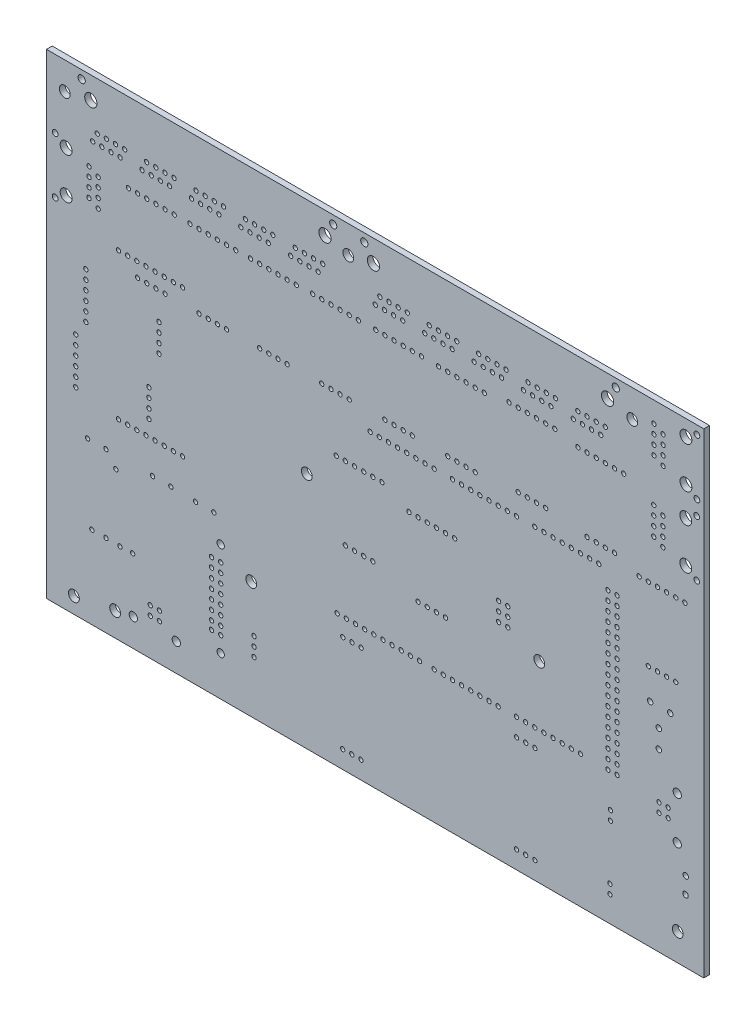
SolidWorks part; units mm, degrees
ref_plane "Front Plane" through (0, 0, 0) normal (0, 0, 1) x (1, 0, 0)
ref_plane "Top Plane" through (0, 0, 0) normal (0, 1, 0) x (1, 0, 0)
ref_plane "Right Plane" through (0, 0, 0) normal (1, 0, 0) x (0, 0, -1)
sketch "Model" plane through (0, 0, 0) normal (0, 0, 1) x (1, 0, 0)
  line L0 (-2.54, -132.08) -> (180, -132.08)
  line L1 (180, -132.08) -> (180, 0)
  line L2 (-2.54, 0) -> (180, 0)
  line L3 (-2.54, -132.08) -> (-2.54, 0)
  line L4 (55.118, -104.267) -> (55.118, -122.428) construction
  line L5 (70.8377, -127.159) -> (150.1297, -127.159) construction
  line L6 (71.3748, -100.203) -> (143.2189, -100.203) construction
  line L7 (154.083, -100.203) -> (154.083, -127.0359) construction
  line L8 (156.083, -101.2392) -> (155.956, -126.5721) construction
  line L9 (158.9458, -104.6525) -> (151.384, -104.6525) construction
  circle A0 centre (175, -109.9998) radius 0.762
  circle A2 centre (21.3998, -109.2497) radius 0.6
  circle A4 centre (10.0742, -109.2244) radius 0.6
  circle A6 centre (13.9749, -109.2495) radius 0.6
  circle A8 centre (165.1, -73.025) radius 0.762
  circle A76 centre (43.307, -99.187) radius 0.6
  circle A78 centre (43.307, -101.727) radius 0.6
  circle A80 centre (43.307, -104.267) radius 0.6
  circle A82 centre (43.307, -106.807) radius 0.6
  circle A84 centre (43.307, -109.347) radius 0.6
  circle A86 centre (43.307, -111.887) radius 0.6
  circle A88 centre (43.307, -114.427) radius 0.6
  circle A90 centre (43.307, -116.713) radius 0.6
  circle A92 centre (45.847, -99.187) radius 0.6
  circle A94 centre (45.847, -101.727) radius 0.6
  circle A96 centre (45.847, -104.267) radius 0.6
  circle A98 centre (45.847, -106.807) radius 0.6
  circle A100 centre (45.847, -109.347) radius 0.6
  circle A102 centre (45.847, -111.887) radius 0.6
  circle A104 centre (45.847, -114.427) radius 0.6
  circle A106 centre (45.847, -116.713) radius 0.6
  circle A108 centre (20, -78.994) radius 0.6
  circle A110 centre (22.54, -78.994) radius 0.6
  circle A112 centre (25.08, -78.994) radius 0.6
  circle A114 centre (27.62, -78.994) radius 0.6
  circle A116 centre (30.16, -78.994) radius 0.6
  circle A118 centre (32.7, -78.994) radius 0.6
  circle A120 centre (35.24, -78.994) radius 0.6
  circle A122 centre (20, -38.354) radius 0.6
  circle A124 centre (22.54, -38.354) radius 0.6
  circle A126 centre (25.08, -38.354) radius 0.6
  circle A128 centre (27.62, -38.354) radius 0.6
  circle A130 centre (30.16, -38.354) radius 0.6
  circle A132 centre (32.7, -38.354) radius 0.6
  circle A134 centre (35.24, -38.354) radius 0.6
  circle A136 centre (167.513, -78.232) radius 0.762
  circle A138 centre (167.513, -83.312) radius 0.762
  circle A140 centre (135.5988, -47.0199) radius 0.6
  circle A142 centre (138.1388, -47.0199) radius 0.6
  circle A144 centre (140.6788, -47.0199) radius 0.6
  circle A146 centre (143.2188, -47.0199) radius 0.6
  circle A148 centre (145.7588, -47.0199) radius 0.6
  circle A150 centre (148.2988, -47.0199) radius 0.6
  circle A152 centre (150.8388, -47.0199) radius 0.6
  circle A154 centre (133.0588, -47.0199) radius 0.6
  circle A156 centre (130.5188, -95.2799) radius 0.6
  circle A158 centre (133.0588, -95.2799) radius 0.6
  circle A160 centre (135.5988, -95.2799) radius 0.6
  circle A162 centre (138.1388, -95.2799) radius 0.6
  circle A164 centre (140.6788, -95.2799) radius 0.6
  circle A166 centre (143.2188, -95.2799) radius 0.6
  circle A168 centre (145.7588, -95.2799) radius 0.6
  circle A170 centre (127.9788, -95.2799) radius 0.6
  circle A172 centre (112.7388, -47.0199) radius 0.6
  circle A174 centre (115.2788, -47.0199) radius 0.6
  circle A176 centre (117.8188, -47.0199) radius 0.6
  circle A178 centre (120.3588, -47.0199) radius 0.6
  circle A180 centre (122.8988, -47.0199) radius 0.6
  circle A182 centre (125.4388, -47.0199) radius 0.6
  circle A184 centre (127.9788, -47.0199) radius 0.6
  circle A186 centre (110.1988, -47.0199) radius 0.6
  circle A188 centre (107.6588, -95.2799) radius 0.6
  circle A190 centre (110.1988, -95.2799) radius 0.6
  circle A192 centre (112.7388, -95.2799) radius 0.6
  circle A194 centre (115.2788, -95.2799) radius 0.6
  circle A196 centre (117.8188, -95.2799) radius 0.6
  circle A198 centre (120.3588, -95.2799) radius 0.6
  circle A200 centre (122.8988, -95.2799) radius 0.6
  circle A202 centre (105.1188, -95.2799) radius 0.6
  circle A204 centre (85.8148, -95.2799) radius 0.6
  circle A206 centre (88.3548, -95.2799) radius 0.6
  circle A208 centre (90.8948, -95.2799) radius 0.6
  circle A210 centre (93.4348, -95.2799) radius 0.6
  circle A212 centre (95.9748, -95.2799) radius 0.6
  circle A214 centre (98.5148, -95.2799) radius 0.6
  circle A216 centre (101.0548, -95.2799) radius 0.6
  circle A218 centre (83.2748, -95.2799) radius 0.6
  circle A220 centre (155.9189, -74.96) radius 0.6
  circle A222 centre (153.3789, -74.96) radius 0.6
  circle A224 centre (155.9189, -77.5) radius 0.6
  circle A226 centre (153.3789, -77.5) radius 0.6
  circle A228 centre (155.9189, -80.04) radius 0.6
  circle A230 centre (153.3789, -80.04) radius 0.6
  circle A232 centre (155.9189, -82.58) radius 0.6
  circle A234 centre (153.3789, -82.58) radius 0.6
  circle A236 centre (155.9189, -85.12) radius 0.6
  circle A238 centre (153.3789, -85.12) radius 0.6
  circle A240 centre (155.9189, -87.66) radius 0.6
  circle A242 centre (153.3789, -87.66) radius 0.6
  circle A244 centre (155.9189, -90.2) radius 0.6
  circle A246 centre (153.3789, -90.2) radius 0.6
  circle A248 centre (155.9189, -92.74) radius 0.6
  circle A250 centre (153.3789, -92.74) radius 0.6
  circle A252 centre (155.9189, -54.64) radius 0.6
  circle A254 centre (153.3789, -54.64) radius 0.6
  circle A256 centre (155.9189, -57.18) radius 0.6
  circle A258 centre (153.3789, -57.18) radius 0.6
  circle A260 centre (155.9189, -59.72) radius 0.6
  circle A262 centre (153.3789, -59.72) radius 0.6
  circle A264 centre (155.9189, -62.26) radius 0.6
  circle A266 centre (153.3789, -62.26) radius 0.6
  circle A268 centre (155.9189, -64.8) radius 0.6
  circle A270 centre (153.3789, -64.8) radius 0.6
  circle A272 centre (155.9189, -67.34) radius 0.6
  circle A274 centre (153.3789, -67.34) radius 0.6
  circle A276 centre (155.9189, -69.88) radius 0.6
  circle A278 centre (153.3789, -69.88) radius 0.6
  circle A280 centre (155.9189, -72.42) radius 0.6
  circle A282 centre (153.3789, -72.42) radius 0.6
  circle A284 centre (153.3788, -52.0999) radius 0.6
  circle A286 centre (155.9188, -52.0999) radius 0.6
  circle A288 centre (153.3788, -95.2799) radius 0.6
  circle A290 centre (155.9188, -95.2799) radius 0.6
  circle A292 centre (92.4188, -47.0199) radius 0.6
  circle A294 centre (94.9588, -47.0199) radius 0.6
  circle A296 centre (97.4988, -47.0199) radius 0.6
  circle A298 centre (100.0388, -47.0199) radius 0.6
  circle A300 centre (102.5788, -47.0199) radius 0.6
  circle A302 centre (105.1188, -47.0199) radius 0.6
  circle A304 centre (80.7348, -95.2799) radius 0.6
  circle A306 centre (78.1948, -95.2799) radius 0.6
  circle A308 centre (87.3388, -47.0199) radius 0.6
  circle A310 centre (89.8788, -47.0199) radius 0.6
  circle A312 centre (123.0258, -74.9599) radius 0.6
  circle A314 centre (125.5658, -74.9599) radius 0.6
  circle A316 centre (123.0258, -72.4199) radius 0.6
  circle A318 centre (125.5658, -72.4199) radius 0.6
  circle A320 centre (123.0258, -69.8799) radius 0.6
  circle A322 centre (125.5658, -69.8799) radius 0.6
  circle A324 centre (55.118, -117.348) radius 0.6
  circle A326 centre (55.118, -114.808) radius 0.6
  circle A328 centre (55.118, -112.268) radius 0.6
  circle A330 centre (154.0739, -104.6525) radius 0.6
  circle A332 centre (154.0739, -107.1925) radius 0.6
  circle A334 centre (153.9469, -124.9725) radius 0.6
  circle A336 centre (153.9469, -122.4325) radius 0.6
  circle A338 centre (127.9935, -127.1614) radius 0.6
  circle A340 centre (130.5335, -127.1614) radius 0.6
  circle A342 centre (133.096, -127.159) radius 0.6
  circle A344 centre (133.096, -100.203) radius 0.6
  circle A346 centre (130.556, -100.203) radius 0.6
  circle A348 centre (128.016, -100.203) radius 0.6
  circle A350 centre (84.7884, -127.1657) radius 0.6
  circle A352 centre (82.2484, -127.1657) radius 0.6
  circle A354 centre (79.7084, -127.1657) radius 0.6
  circle A356 centre (84.836, -100.203) radius 0.6
  circle A358 centre (82.296, -100.203) radius 0.6
  circle A360 centre (79.756, -100.203) radius 0.6
  circle A362 centre (43.942, -88.138) radius 0.6
  circle A364 centre (38.862, -88.138) radius 0.6
  circle A366 centre (170.0997, -98.5698) radius 0.6
  circle A368 centre (167.5597, -98.5698) radius 0.6
  circle A370 centre (170.0997, -96.0298) radius 0.6
  circle A372 centre (172.6397, -91.3308) radius 1.15
  circle A374 centre (172.6397, -103.2688) radius 1.15
  circle A376 centre (26.2799, -121.8247) radius 0.6
  circle A378 centre (26.28, -119.2848) radius 0.6
  circle A380 centre (28.82, -121.8247) radius 0.6
  circle A382 centre (33.519, -124.3647) radius 1.15
  circle A384 centre (21.581, -124.3647) radius 1.15
  circle A386 centre (8.89, -87.884) radius 0.6
  circle A388 centre (13.97, -87.884) radius 0.6
  circle A390 centre (26.924, -87.884) radius 0.6
  circle A392 centre (32.004, -87.884) radius 0.6
  circle A394 centre (10.2869, -15.7479) radius 0.6
  circle A396 centre (11.5569, -13.2079) radius 0.6
  circle A398 centre (12.8269, -15.7479) radius 0.6
  circle A400 centre (14.0969, -13.2079) radius 0.6
  circle A402 centre (15.3669, -15.7479) radius 0.6
  circle A404 centre (16.6369, -13.2079) radius 0.6
  circle A406 centre (17.9069, -15.7479) radius 0.6
  circle A408 centre (19.1769, -13.2079) radius 0.6
  circle A410 centre (24.0029, -15.7479) radius 0.6
  circle A412 centre (25.2729, -13.2079) radius 0.6
  circle A414 centre (26.5429, -15.7479) radius 0.6
  circle A416 centre (27.8129, -13.2079) radius 0.6
  circle A419 centre (29.083, -15.748) radius 0.6
  circle A420 centre (30.3529, -13.2079) radius 0.6
  circle A422 centre (31.6229, -15.7479) radius 0.6
  circle A424 centre (32.8929, -13.2079) radius 0.6
  circle A426 centre (37.7189, -15.7479) radius 0.6
  circle A428 centre (38.9889, -13.2079) radius 0.6
  circle A430 centre (40.2589, -15.7479) radius 0.6
  circle A432 centre (41.5289, -13.2079) radius 0.6
  circle A434 centre (42.7989, -15.7479) radius 0.6
  circle A436 centre (44.0689, -13.2079) radius 0.6
  circle A438 centre (45.3389, -15.7479) radius 0.6
  circle A440 centre (46.6089, -13.2079) radius 0.6
  circle A442 centre (51.4349, -15.7479) radius 0.6
  circle A444 centre (52.7049, -13.2079) radius 0.6
  circle A446 centre (53.9749, -15.7479) radius 0.6
  circle A448 centre (55.2449, -13.2079) radius 0.6
  circle A450 centre (56.5149, -15.7479) radius 0.6
  circle A452 centre (57.7849, -13.2079) radius 0.6
  circle A454 centre (59.0549, -15.7479) radius 0.6
  circle A456 centre (60.3249, -13.2079) radius 0.6
  circle A458 centre (7.2389, -2.2859) radius 1
  circle A460 centre (77.0889, -2.2859) radius 1
  circle A462 centre (74.168, -13.208) radius 0.6
  circle A464 centre (72.898, -15.748) radius 0.6
  circle A466 centre (71.628, -13.208) radius 0.6
  circle A468 centre (70.358, -15.748) radius 0.6
  circle A470 centre (69.088, -13.208) radius 0.6
  circle A472 centre (67.818, -15.748) radius 0.6
  circle A474 centre (66.548, -13.208) radius 0.6
  circle A476 centre (65.278, -15.748) radius 0.6
  circle A478 centre (88.7729, -15.7479) radius 0.6
  circle A480 centre (90.0429, -13.2079) radius 0.6
  circle A482 centre (91.3129, -15.7479) radius 0.6
  circle A484 centre (92.5829, -13.2079) radius 0.6
  circle A486 centre (93.8529, -15.7479) radius 0.6
  circle A488 centre (95.1229, -13.2079) radius 0.6
  circle A490 centre (96.3929, -15.7479) radius 0.6
  circle A492 centre (97.6629, -13.2079) radius 0.6
  circle A494 centre (102.4889, -15.7479) radius 0.6
  circle A496 centre (103.7589, -13.2079) radius 0.6
  circle A498 centre (105.0289, -15.7479) radius 0.6
  circle A500 centre (106.2989, -13.2079) radius 0.6
  circle A502 centre (107.5689, -15.7479) radius 0.6
  circle A504 centre (108.8389, -13.2079) radius 0.6
  circle A506 centre (110.1089, -15.7479) radius 0.6
  circle A508 centre (111.3789, -13.2079) radius 0.6
  circle A510 centre (116.2049, -15.7479) radius 0.6
  circle A512 centre (117.4749, -13.2079) radius 0.6
  circle A514 centre (118.7449, -15.7479) radius 0.6
  circle A516 centre (120.0149, -13.2079) radius 0.6
  circle A518 centre (121.2849, -15.7479) radius 0.6
  circle A520 centre (122.5549, -13.2079) radius 0.6
  circle A522 centre (123.8249, -15.7479) radius 0.6
  circle A524 centre (125.0949, -13.2079) radius 0.6
  circle A526 centre (129.9209, -15.7479) radius 0.6
  circle A528 centre (131.1909, -13.2079) radius 0.6
  circle A530 centre (132.4609, -15.7479) radius 0.6
  circle A532 centre (133.7309, -13.2079) radius 0.6
  circle A534 centre (135.0009, -15.7479) radius 0.6
  circle A536 centre (136.2709, -13.2079) radius 0.6
  circle A538 centre (137.5409, -15.7479) radius 0.6
  circle A540 centre (138.8109, -13.2079) radius 0.6
  circle A542 centre (85.7249, -2.2859) radius 1
  circle A544 centre (155.5749, -2.2859) radius 1
  circle A546 centre (152.654, -13.208) radius 0.6
  circle A548 centre (151.384, -15.748) radius 0.6
  circle A550 centre (150.114, -13.208) radius 0.6
  circle A552 centre (148.844, -15.748) radius 0.6
  circle A554 centre (147.574, -13.208) radius 0.6
  circle A556 centre (146.304, -15.748) radius 0.6
  circle A558 centre (145.034, -13.208) radius 0.6
  circle A560 centre (143.764, -15.748) radius 0.6
  circle A562 centre (168.6946, -14.57) radius 0.6
  circle A564 centre (166.1546, -13.3) radius 0.6
  circle A566 centre (168.6946, -12.03) radius 0.6
  circle A568 centre (166.1546, -10.76) radius 0.6
  circle A570 centre (168.6946, -9.49) radius 0.6
  circle A572 centre (166.1546, -8.22) radius 0.6
  circle A574 centre (168.6946, -6.95) radius 0.6
  circle A576 centre (166.1546, -5.68) radius 0.6
  circle A578 centre (178.0946, -2.375) radius 0.8
  circle A580 centre (178.0946, -17.875) radius 0.8
  circle A582 centre (168.6446, -34.1449) radius 0.6
  circle A584 centre (166.1046, -32.8749) radius 0.6
  circle A586 centre (168.6446, -31.6049) radius 0.6
  circle A588 centre (166.1046, -30.3349) radius 0.6
  circle A590 centre (168.6446, -29.0649) radius 0.6
  circle A592 centre (166.1046, -27.7949) radius 0.6
  circle A594 centre (168.6446, -26.5249) radius 0.6
  circle A596 centre (166.1046, -25.2549) radius 0.6
  circle A598 centre (178.0447, -21.9499) radius 0.8
  circle A600 centre (178.0447, -37.4499) radius 0.8
  circle A602 centre (9.272, -22.225) radius 0.6
  circle A604 centre (11.812, -23.495) radius 0.6
  circle A606 centre (9.272, -24.765) radius 0.6
  circle A608 centre (11.812, -26.035) radius 0.6
  circle A610 centre (9.272, -27.305) radius 0.6
  circle A612 centre (11.812, -28.575) radius 0.6
  circle A614 centre (9.272, -29.845) radius 0.6
  circle A616 centre (11.812, -31.115) radius 0.6
  circle A618 centre (-0.128, -34.42) radius 0.8
  circle A620 centre (-0.128, -18.92) radius 0.8
  circle A622 centre (28.72, -52.4799) radius 0.6
  circle A624 centre (28.72, -55.0199) radius 0.6
  circle A626 centre (28.72, -57.5599) radius 0.6
  circle A628 centre (8.4, -47.3999) radius 0.6
  circle A630 centre (8.4, -49.9399) radius 0.6
  circle A632 centre (8.4, -52.4799) radius 0.6
  circle A634 centre (8.4, -55.0199) radius 0.6
  circle A636 centre (8.4, -57.5599) radius 0.6
  circle A638 centre (27.8449, -42.32) radius 0.6
  circle A640 centre (25.3049, -42.32) radius 0.6
  circle A642 centre (22.7649, -42.32) radius 0.6
  circle A644 centre (32.9249, -22) radius 0.6
  circle A646 centre (30.3849, -22) radius 0.6
  circle A648 centre (27.8449, -22) radius 0.6
  circle A650 centre (25.3049, -22) radius 0.6
  circle A652 centre (22.7649, -22) radius 0.6
  circle A654 centre (44.9199, -42.3449) radius 0.6
  circle A656 centre (42.3799, -42.3449) radius 0.6
  circle A658 centre (39.8399, -42.3449) radius 0.6
  circle A660 centre (49.9999, -22.0249) radius 0.6
  circle A662 centre (47.4599, -22.0249) radius 0.6
  circle A664 centre (44.9199, -22.0249) radius 0.6
  circle A666 centre (42.3799, -22.0249) radius 0.6
  circle A668 centre (39.8399, -22.0249) radius 0.6
  circle A669 centre (39.8399, -22.0249) radius 0.6
  circle A670 centre (61.7449, -42.295) radius 0.6
  circle A672 centre (59.2049, -42.295) radius 0.6
  circle A674 centre (56.6649, -42.295) radius 0.6
  circle A676 centre (66.8249, -21.975) radius 0.6
  circle A678 centre (64.2849, -21.975) radius 0.6
  circle A680 centre (61.7449, -21.975) radius 0.6
  circle A682 centre (59.2049, -21.975) radius 0.6
  circle A684 centre (56.6649, -21.975) radius 0.6
  circle A686 centre (78.9948, -42.17) radius 0.6
  circle A688 centre (76.4548, -42.17) radius 0.6
  circle A690 centre (73.9148, -42.17) radius 0.6
  circle A692 centre (84.0748, -21.85) radius 0.6
  circle A694 centre (81.5348, -21.85) radius 0.6
  circle A696 centre (78.9948, -21.85) radius 0.6
  circle A698 centre (76.4548, -21.85) radius 0.6
  circle A700 centre (73.9148, -21.85) radius 0.6
  circle A702 centre (96.5198, -42.07) radius 0.6
  circle A704 centre (93.9798, -42.07) radius 0.6
  circle A706 centre (91.4398, -42.07) radius 0.6
  circle A708 centre (101.5998, -21.75) radius 0.6
  circle A710 centre (99.0598, -21.75) radius 0.6
  circle A712 centre (96.5198, -21.75) radius 0.6
  circle A714 centre (93.9798, -21.75) radius 0.6
  circle A716 centre (91.4398, -21.75) radius 0.6
  circle A718 centre (113.9698, -42.145) radius 0.6
  circle A720 centre (111.4298, -42.145) radius 0.6
  circle A722 centre (108.8898, -42.145) radius 0.6
  circle A724 centre (119.0498, -21.825) radius 0.6
  circle A726 centre (116.5098, -21.825) radius 0.6
  circle A728 centre (113.9698, -21.825) radius 0.6
  circle A730 centre (111.4298, -21.825) radius 0.6
  circle A732 centre (108.8898, -21.825) radius 0.6
  circle A734 centre (85.5448, -77.8199) radius 0.6
  circle A736 centre (83.0048, -77.8199) radius 0.6
  circle A738 centre (80.4648, -77.8199) radius 0.6
  circle A740 centre (90.6248, -57.4999) radius 0.6
  circle A742 centre (88.0848, -57.4999) radius 0.6
  circle A744 centre (85.5448, -57.4999) radius 0.6
  circle A746 centre (83.0048, -57.4999) radius 0.6
  circle A748 centre (80.4648, -57.4999) radius 0.6
  circle A750 centre (133.5447, -40.995) radius 0.6
  circle A752 centre (131.0047, -40.995) radius 0.6
  circle A754 centre (128.4647, -40.995) radius 0.6
  circle A756 centre (138.6247, -20.675) radius 0.6
  circle A758 centre (136.0847, -20.675) radius 0.6
  circle A760 centre (133.5447, -20.675) radius 0.6
  circle A762 centre (131.0047, -20.675) radius 0.6
  circle A764 centre (128.4647, -20.675) radius 0.6
  circle A766 centre (105.7448, -81.2449) radius 0.6
  circle A768 centre (103.2048, -81.2449) radius 0.6
  circle A770 centre (100.6648, -81.2449) radius 0.6
  circle A772 centre (110.8248, -60.9249) radius 0.6
  circle A774 centre (108.2848, -60.9249) radius 0.6
  circle A776 centre (105.7448, -60.9249) radius 0.6
  circle A778 centre (103.2048, -60.9249) radius 0.6
  circle A780 centre (100.6648, -60.9249) radius 0.6
  circle A782 centre (152.6697, -42.22) radius 0.6
  circle A784 centre (150.1297, -42.22) radius 0.6
  circle A786 centre (147.5897, -42.22) radius 0.6
  circle A788 centre (157.7497, -21.9) radius 0.6
  circle A790 centre (155.2097, -21.9) radius 0.6
  circle A792 centre (152.6697, -21.9) radius 0.6
  circle A794 centre (150.1297, -21.9) radius 0.6
  circle A796 centre (147.5897, -21.9) radius 0.6
  circle A798 centre (169.672, -64.77) radius 0.6
  circle A800 centre (167.132, -64.77) radius 0.6
  circle A802 centre (164.592, -64.77) radius 0.6
  circle A804 centre (174.752, -44.45) radius 0.6
  circle A806 centre (172.212, -44.45) radius 0.6
  circle A808 centre (169.672, -44.45) radius 0.6
  circle A810 centre (167.132, -44.45) radius 0.6
  circle A812 centre (164.592, -44.45) radius 0.6
  circle A814 centre (25.908, -69.596) radius 0.6
  circle A816 centre (25.908, -72.136) radius 0.6
  circle A818 centre (25.908, -74.676) radius 0.6
  circle A820 centre (5.588, -64.516) radius 0.6
  circle A822 centre (5.588, -67.056) radius 0.6
  circle A824 centre (5.588, -69.596) radius 0.6
  circle A826 centre (5.588, -72.136) radius 0.6
  circle A828 centre (5.588, -74.676) radius 0.6
  circle A830 centre (17.8748, -109.3493) radius 0.6
  circle A831 centre (174.9246, -114.5748) radius 0.762
  circle A832 centre (170.6881, -73.025) radius 0.762
  circle A833 centre (17.46, -78.994) radius 0.6
  circle A834 centre (17.46, -38.354) radius 0.6
  circle A835 centre (167.5597, -96.0298) radius 0.6
  circle A836 centre (28.82, -119.2848) radius 0.6
  circle A837 centre (28.72, -49.9399) radius 0.6
  circle A838 centre (8.4, -60.0999) radius 0.6
  circle A839 centre (30.3849, -42.32) radius 0.6
  circle A840 centre (20.2249, -22) radius 0.6
  circle A841 centre (47.4599, -42.3449) radius 0.6
  circle A842 centre (37.2999, -22.0249) radius 0.6
  circle A843 centre (64.2849, -42.295) radius 0.6
  circle A844 centre (54.1249, -21.975) radius 0.6
  circle A845 centre (81.5348, -42.17) radius 0.6
  circle A846 centre (71.3748, -21.85) radius 0.6
  circle A847 centre (99.0598, -42.07) radius 0.6
  circle A848 centre (88.8998, -21.75) radius 0.6
  circle A849 centre (116.5098, -42.145) radius 0.6
  circle A850 centre (106.3498, -21.825) radius 0.6
  circle A851 centre (88.0848, -77.8199) radius 0.6
  circle A852 centre (77.9248, -57.4999) radius 0.6
  circle A853 centre (136.0847, -40.995) radius 0.6
  circle A854 centre (125.9247, -20.675) radius 0.6
  circle A855 centre (108.2848, -81.2449) radius 0.6
  circle A856 centre (98.1248, -60.9249) radius 0.6
  circle A857 centre (155.2097, -42.22) radius 0.6
  circle A858 centre (145.0497, -21.9) radius 0.6
  circle A859 centre (172.212, -64.77) radius 0.6
  circle A860 centre (162.052, -44.45) radius 0.6
  circle A861 centre (25.908, -67.056) radius 0.6
  circle A862 centre (5.588, -77.216) radius 0.6
  circle A863 centre (54.3499, -99.5749) radius 1.5
  circle A864 centre (81.2749, -7.6251) radius 1.5
  circle A865 centre (5.08, -127.635) radius 1.5
  circle A866 centre (16.5242, -125.4491) radius 1.5
  circle A867 centre (16.7241, -91.3239) radius 0.6
  circle A868 centre (2.54, -7.62) radius 1.5
  circle A869 centre (160.1498, -7.6751) radius 1.5
  circle A870 centre (172.7746, -124.4999) radius 1.5
  circle A871 centre (69.7499, -65.9249) radius 1.5
  circle A872 centre (134.3249, -78.7499) radius 1.5
  circle A873 centre (45.847, -121.031) radius 1.016
  circle A874 centre (45.847, -94.869) radius 1.016
  circle A875 centre (74.803, -6.096) radius 1.7
  circle A876 centre (9.779, -6.096) radius 1.7
  circle A877 centre (153.289, -6.096) radius 1.7
  circle A878 centre (88.265, -6.096) radius 1.7
  circle A879 centre (175.0446, -4.4099) radius 1.65
  circle A880 centre (175.0446, -15.8399) radius 1.65
  circle A881 centre (174.9946, -23.985) radius 1.65
  circle A882 centre (174.9946, -35.415) radius 1.65
  circle A883 centre (2.922, -32.385) radius 1.65
  circle A884 centre (2.922, -20.955) radius 1.65
  point P22 (0, 0)
  point P23 (0, 0)
  point P24 (0, 0)
  point P25 (0, 0)
  point P26 (0, 0)
  dimension "D3" = 1.2
  dimension "D1" = 25.917
  dimension "D2" = 4.921
extrude "Boss-Extrude1" add sketch "Model" along normal blind 1.6
